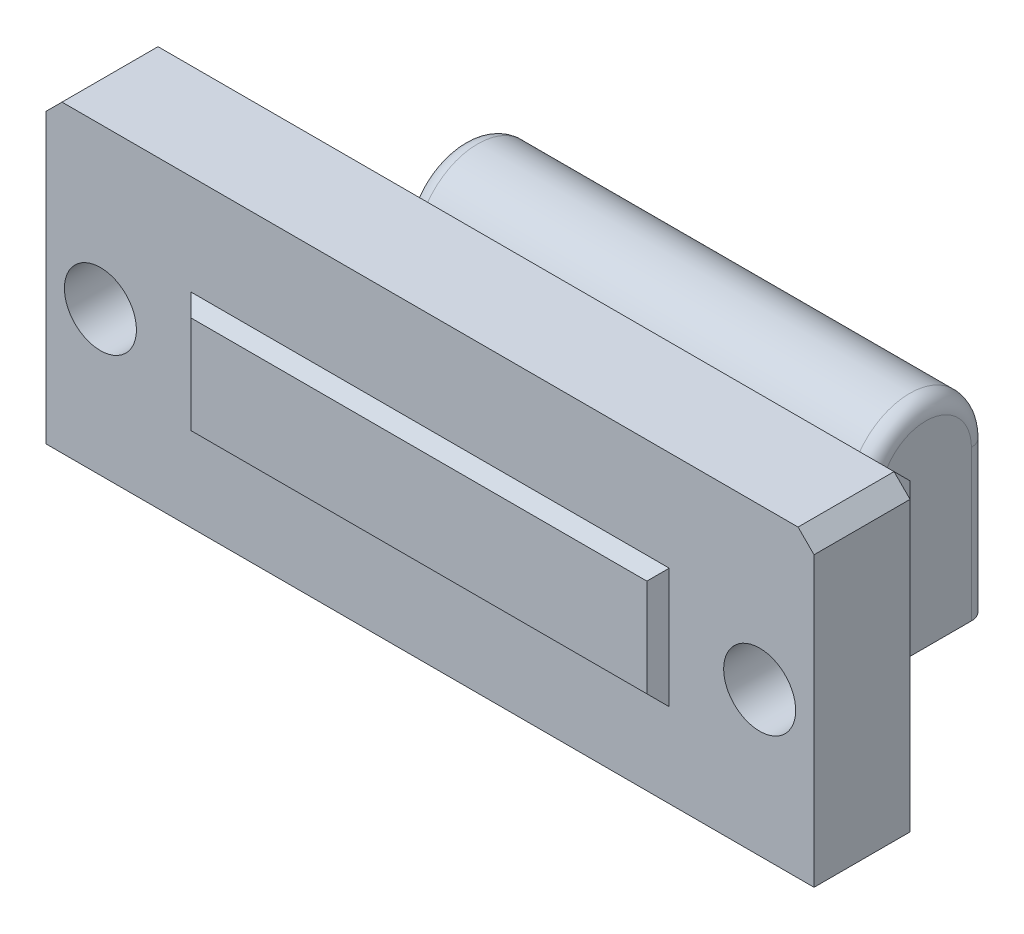
SolidWorks part; units mm, degrees
ref_plane "Front" through (0, 0, 0) normal (0, 0, 1) x (1, 0, 0)
ref_plane "Top" through (0, 0, 0) normal (0, 1, 0) x (1, 0, 0)
ref_plane "Right" through (0, 0, 0) normal (1, 0, 0) x (0, 0, -1)
sketch "Skizze2" plane through (0, 0, 0) normal (1, 0, 0) x (0, 0, -1)
  line L4 (1.5483, 7.2744) -> (-3, 7.2744)
  line L5 (10.3338, -0.9256) -> (-3, -0.9256)
  line L7 (1.5483, 7.2744) -> (2.8674, 10.8155)
  line L8 (1.5, 7.5744) -> (2.7573, 10.9496) construction
  line L9 (10.3338, 9.47) -> (10.3338, -0.9256)
  line L11 (6.4794, 13.3244) -> (1.8107, 13.3244) construction
  line L12 (-3, 7.2744) -> (-3, -0.9256)
  line L13 (0, 39.381) -> (0, -8.9055) construction
  line L14 (-3, 7.2744) -> (-3, 19.0744)
  line L15 (-3, 19.0744) -> (-10, 19.0744)
  line L16 (-10, 19.0744) -> (-10, -0.9256)
  line L17 (-10, -0.9256) -> (-3, -0.9256)
  line L18 (1.5, 7.5744) -> (1, 7.5744) construction
  arc A0 (2.8674, 10.8155) -> (10.3338, 9.47) centre (6.4794, 9.47) cw
  arc A1 (2.7573, 10.9496) -> (10.4847, 9.4912) centre (6.4794, 9.47) cw construction
  dimension "D1" = 0.3
  dimension "D2" = 0.3
  dimension "D3" = 14.25
  dimension "D4" = 3
  dimension "D5" = 20
  dimension "D6" = 7
extrude "Aufsatz-Linear austragen1" add sketch "Skizze2" along normal mid plane 29 contours A0 L7 L4 L12 L5 L9 region at (0, 5.0341, -4.4013)
extrude "Aufsatz-Linear austragen2" add sketch "Skizze2<3>" along normal mid plane 48 contours L16 L17 L12 L14 L15 region at (0, 9.0744, 6.5)
sketch "Skizze2<3>" plane through (0, 0, 0) normal (1, 0, 0) x (0, 0, -1) same geometry as "Skizze2"
sketch "Skizze5" plane through (0, 0, 3) normal (0, 0, -1) x (-1, 0, 0)
  line L0 (-24, 9.0744) -> (24, 9.0744) construction
  line L1 (-24, 19.0744) -> (-24, -0.9256) construction
  line L2 (24, 19.0744) -> (24, -0.9256) construction
  line L3 (0, 9.0744) -> (0, -4.4205) construction
  circle A0 centre (-20.6, 9.0744) radius 2.25
  circle A1 centre (20.6, 9.0744) radius 2.25
  dimension "D1" = 4.5
  dimension "D2" = 3.4
extrude "Schnitt-Linear austragen1" cut sketch "Skizze5" against normal through all
sketch "Skizze6" plane through (0, 0, 0) normal (-1, 0, 0) x (0, 0, 1)
  line L0 (10, 19.0744) -> (10, -0.9256) construction
  line L1 (10, 9.0744) -> (20.2548, 9.0744) construction
  line L2 (10, 12.8244) -> (10.7, 12.1244)
  line L3 (10.7, 12.1244) -> (10.7, 6.0244)
  line L4 (10, 12.8244) -> (10, 5.3244)
  line L5 (10, 5.3244) -> (10.7, 6.0244)
  point P11 (10.7, 9.0744)
  dimension "D1" = 45
  dimension "D2" = 0.7
  dimension "D3" = 7.5
extrude "Aufsatz-Linear austragen4" add sketch "Skizze6" along normal mid plane 30
fillet "Verrundung1" radius 3 3 edges at (14.5, 3.1744, 3) (-14.5, 3.1744, 3) (0, 7.2744, 3)
fillet "Verrundung2" radius 1 10 edges at (14.5, 9.0449, -2.2078) (14.5, 13.2633, -7.1629) (-14.5, 9.0449, -2.2078) (-14.5, 13.2633, -7.1629) (14.5, 4.2722, -10.3338) (-14.5, 4.2722, -10.3338) (14.5, 7.2744, -0.7742) (-14.5, 7.2744, -0.7742) (15.3787, 8.1531, 2.1213) (-15.3787, 8.1531, 2.1213)
chamfer "Fase1" distance 1 angle 45 17 edges at (20.75, -0.9256, 3) (15.3787, -0.9256, 2.1213) (14.5, -0.9256, -4.6669) (14.2071, -0.9256, -10.0409) (0, -0.9256, -10.3338) (-14.2071, -0.9256, -10.0409) (-14.5, -0.9256, -4.6669) (-15.3787, -0.9256, 2.1213) (24, -0.9256, 6.5) (0, -0.9256, 10) (-24, -0.9256, 6.5) (-20.75, -0.9256, 3) (24, 19.0744, 6.5) (-24, 19.0744, 6.5) (0, 19.0744, 3) (24, 9.0744, 3) (-24, 9.0744, 3)
chamfer "Fase2" distance 0.75 angle 45 2 edges at (15, 9.0744, 10.7) (-15, 9.0744, 10.7)
sketch "Skizze9" plane through (24, 0, 0) normal (1, 0, 0) x (0, 0, -1)
  line L0 (-10, 18.0744) -> (-3, 18.0744) construction
  line L1 (-6.5, 18.0744) -> (-6.5, -2.0185) construction
  circle A0 centre (-6.5, 16.8296) radius 1.2
  circle A1 centre (-6.5, 13.784) radius 1.425
  circle A2 centre (-6.5, 4.2866) radius 1.775
  dimension "D1" = 2.4
  dimension "D2" = 2.85
  dimension "D3" = 3.55
extrude "Schnitt-Linear austragen3" [suppressed] cut sketch "Skizze9" against normal through all
chamfer "Fase3" [suppressed] distance 0.75 angle 45
